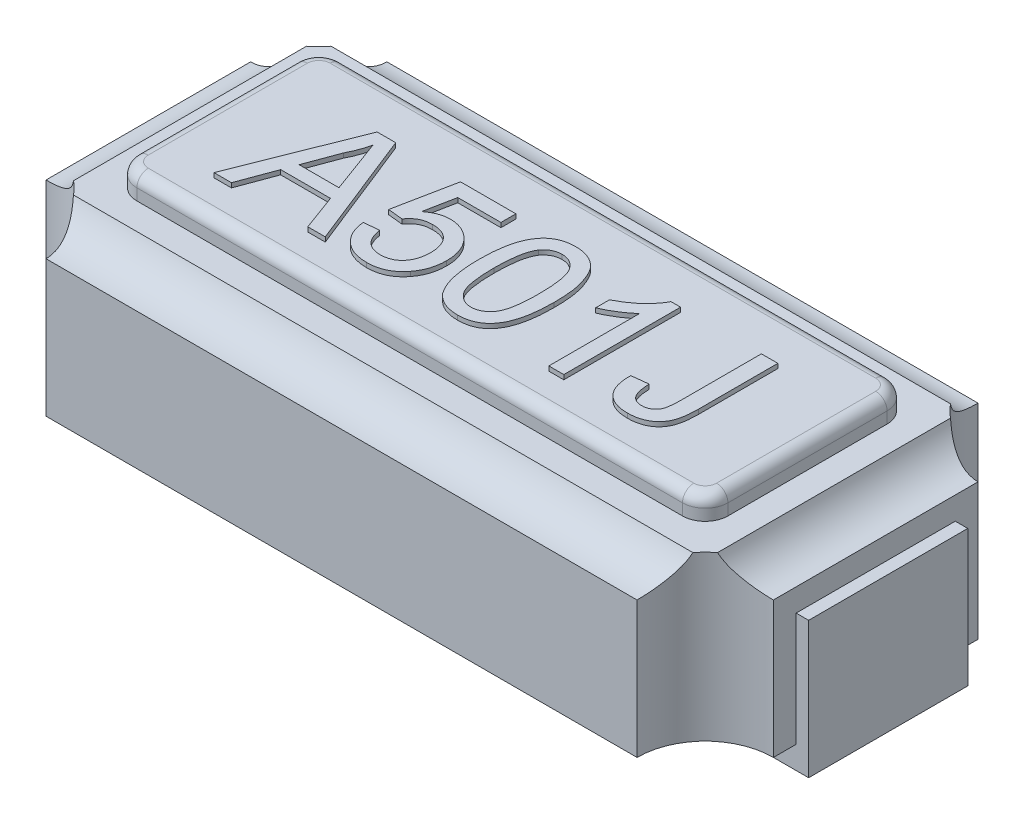
SolidWorks part; units mm, degrees
ref_plane "Спереди" through (0, 0, 0) normal (0, 0, 1) x (1, 0, 0)
ref_plane "Сверху" through (0, 0, 0) normal (0, 1, 0) x (1, 0, 0)
ref_plane "Справа" through (0, 0, 0) normal (1, 0, 0) x (0, 0, -1)
ref_plane "Плоскость1" through (0, 0.1, 0) normal (0, 1, 0) x (1, 0, 0)
sketch "Эскиз1" plane through (0, 0.1, 0) normal (0, 1, 0) x (1, 0, 0)
  line L0 (-1.3, 0.75) -> (1.3, 0.75)
  line L1 (-1.6, -0.75) -> (1.6, -0.75) construction
  line L2 (-1.6, -0.75) -> (-1.6, 0.75) construction
  line L3 (-1.6, 0.75) -> (1.6, 0.75) construction
  line L4 (1.6, -0.75) -> (1.6, 0.75) construction
  line L5 (-1.6, -0.75) -> (1.6, 0.75) construction
  line L6 (-1.6, 0.75) -> (1.6, -0.75) construction
  line L7 (-1.6, 0.45) -> (-1.6, -0.45)
  line L8 (-1.3, -0.75) -> (1.3, -0.75)
  line L9 (1.6, -0.45) -> (1.6, 0.45)
  arc A0 (-1.6, 0.45) -> (-1.3, 0.75) centre (-1.6, 0.75) ccw
  arc A1 (-1.3, -0.75) -> (-1.6, -0.45) centre (-1.6, -0.75) ccw
  arc A2 (1.6, 0.45) -> (1.3, 0.75) centre (1.6, 0.75) cw
  arc A3 (1.3, -0.75) -> (1.6, -0.45) centre (1.6, -0.75) cw
  point P0 (0, 0)
extrude "Бобышка-Вытянуть1" add sketch "Эскиз1" along normal blind 0.8
sketch "Эскиз3" plane through (0, 0, 0) normal (1, 0, 0) x (0, 0, -1)
  circle A0 centre (-0.75, 0.9) radius 0.2
sketch "Эскиз4" plane through (0, 0, 0) normal (0, 0, 1) x (1, 0, 0)
  circle A0 centre (1.6, 0.9) radius 0.2
extrude "Бобышка-Вытянуть4" add sketch "Эскиз3" along normal blind 3.2 from offset 1.6 separate body offset against normal yes
extrude "Бобышка-Вытянуть5" add sketch "Эскиз4" along normal blind 1.5 from offset 0.75 separate body offset against normal yes
pattern_linear "Линейный массив3" count 2 spacing 1.5 along (0, 0, -1) of "Бобышка-Вытянуть4"
pattern_linear "Линейный массив4" count 2 spacing 3.2 along (-1, 0, 0) of "Бобышка-Вытянуть5"
combine bodies "Соединить1" operation type subtract main body 103 bodies to subtract 108 111 110 109
sketch "Эскиз5" plane through (0, 0, 0) normal (0, 1, 0) x (1, 0, 0)
  line L1 (0.855, -0.35) -> (1.655, -0.35)
  line L2 (0.855, -0.35) -> (0.855, 0.35)
  line L3 (0.855, 0.35) -> (1.655, 0.35)
  line L4 (1.655, -0.35) -> (1.655, 0.35)
  line L5 (0.855, -0.35) -> (1.655, 0.35) construction
  line L6 (0.855, 0.35) -> (1.655, -0.35) construction
  line L7 (-0.855, -0.35) -> (-1.655, -0.35)
  line L8 (-0.855, -0.35) -> (-0.855, 0.35)
  line L9 (-0.855, 0.35) -> (-1.655, 0.35)
  line L10 (-1.655, -0.35) -> (-1.655, 0.35)
  line L11 (-0.855, -0.35) -> (-1.655, 0.35) construction
  line L12 (-0.855, 0.35) -> (-1.655, -0.35) construction
  point P0 (1.255, 0)
  point P5 (-1.255, 0)
  point P10 (0, 0)
  point P11 (0, 0)
  point P12 (0, 0)
  point P13 (0, 0)
  point P14 (0, 0)
  point P15 (0, 0)
  point P16 (0, 0)
  point P17 (0, 0)
  point P18 (0, 0)
  point P19 (0, 0)
  point P20 (0, 0)
  point P21 (0, 0)
extrude "Бобышка-Вытянуть6" add sketch "Эскиз5" along normal blind 0.6 separate body
combine bodies "Соединить2" operation type subtract main body 112 bodies to subtract 114 113
extrude "Бобышка-Вытянуть7" add sketch "Эскиз5<2>" along normal blind 0.6 separate body
sketch "Эскиз5<2>" plane through (0, 0, 0) normal (0, 1, 0) x (1, 0, 0) same geometry as "Эскиз5"
sketch "Эскиз6" plane through (0, 0.9, 0) normal (0, 1, 0) x (1, 0, 0)
  line L1 (-1.45, -0.6) -> (1.45, -0.6)
  line L2 (-1.45, -0.6) -> (-1.45, 0.6)
  line L3 (-1.45, 0.6) -> (1.45, 0.6)
  line L4 (1.45, -0.6) -> (1.45, 0.6)
  line L5 (-1.45, -0.6) -> (1.45, 0.6) construction
  line L6 (-1.45, 0.6) -> (1.45, -0.6) construction
  point P0 (0, 0)
extrude "Бобышка-Вытянуть8" add sketch "Эскиз6" against normal blind 0.08 separate body
combine bodies "Соединить3" operation type subtract main body 115 bodies to subtract 117
sketch "Эскиз7" plane through (0, 0.82, 0) normal (0, 1, 0) x (1, 0, 0)
  line L1 (-1.2, 0.45) -> (1.2, 0.45)
  line L2 (-1.3, 0.35) -> (-1.3, -0.35)
  line L3 (-1.2, -0.45) -> (1.2, -0.45)
  line L4 (1.3, 0.35) -> (1.3, -0.35)
  line L5 (-1.3, 0.45) -> (1.3, -0.45) construction
  line L6 (-1.3, -0.45) -> (1.3, 0.45) construction
  arc A0 (1.2, -0.45) -> (1.3, -0.35) centre (1.2, -0.35) ccw
  arc A1 (1.2, 0.45) -> (1.3, 0.35) centre (1.2, 0.35) cw
  arc A2 (-1.2, 0.45) -> (-1.3, 0.35) centre (-1.2, 0.35) ccw
  arc A3 (-1.3, -0.35) -> (-1.2, -0.45) centre (-1.2, -0.35) ccw
  point P0 (0, 0)
  dimension "D1" = 0.1
extrude "Бобышка-Вытянуть9" add sketch "Эскиз7" along normal blind 0.1 separate body contours L3 A0 L4 A1 L1 A2 L2 A3
sketch "Эскиз8" plane through (0, 0.92, 0) normal (0, 1, 0) x (1, 0, 0)
  line L1 (-1.1139, -0.2924) -> (1.1139, -0.2924) construction
  line L2 (-1.1139, -0.2924) -> (-1.1139, 0.2924) construction
  line L3 (-1.1139, 0.2924) -> (1.1139, 0.2924) construction
  line L4 (1.1139, -0.2924) -> (1.1139, 0.2924) construction
  line L5 (-1.1139, -0.2924) -> (1.1139, 0.2924) construction
  line L6 (-1.1139, 0.2924) -> (1.1139, -0.2924) construction
  text T0 "A501J" font "Arial" height in points 2
  point P0 (0, 0)
extrude "Бобышка-Вытянуть10" add sketch "Эскиз8" along normal blind 0.02 separate body
fillet "Скругление1" radius 0.05 8 edges at (-1.3, 0.92, 0) (-1.2707, 0.92, -0.4207) (0, 0.92, -0.45) (1.2707, 0.92, -0.4207) (1.3, 0.92, 0) (1.2707, 0.92, 0.4207) (0, 0.92, 0.45) (-1.2707, 0.92, 0.4207)
